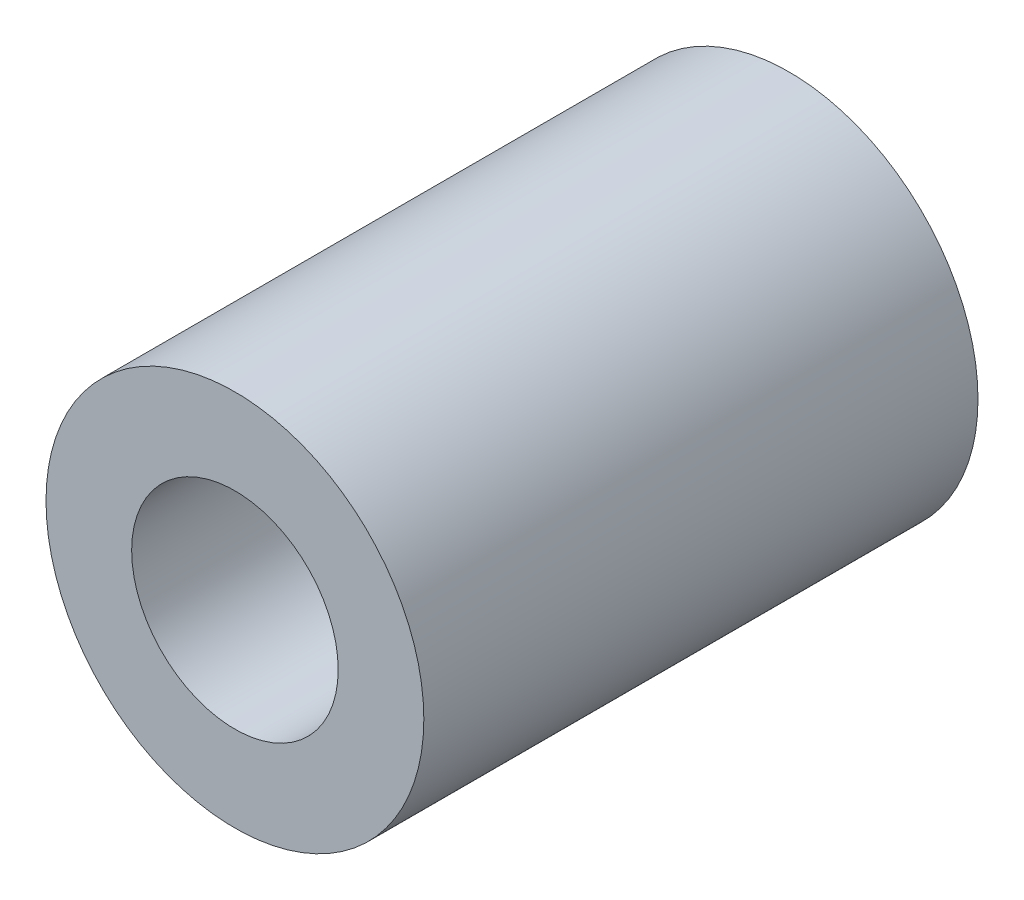
SolidWorks part; units mm, degrees
ref_plane "Front Plane" through (0, 0, 0) normal (0, 0, 1) x (1, 0, 0)
ref_plane "Top Plane" through (0, 0, 0) normal (0, 1, 0) x (1, 0, 0)
ref_plane "Right Plane" through (0, 0, 0) normal (1, 0, 0) x (0, 0, -1)
sketch "Sketch1" plane through (0, 0, 0) normal (0, 0, 1) x (1, 0, 0)
  circle A0 centre (0, 0) radius 7.5
  circle A1 centre (0, 0) radius 4.1
  point P3 (2.061, 3.5)
  dimension "D1" = 15
  dimension "D2" = 8.2
extrude "Boss-Extrude1" add sketch "Sketch1" along normal blind 22 contours A0 A1 region at (-7.2879, 0, 0)
